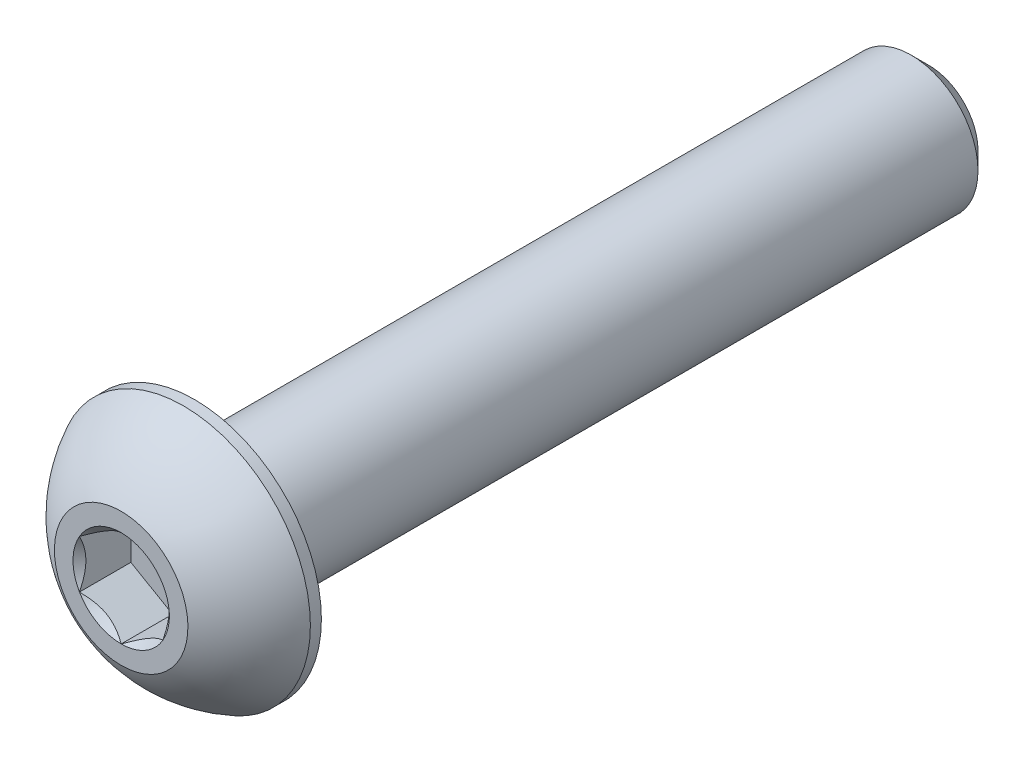
SolidWorks part; units mm, degrees
material "Alloy Steel"
ref_plane "Front" through (0, 0, 0) normal (0, 0, 1) x (1, 0, 0)
ref_plane "Top" through (0, 0, 0) normal (0, 1, 0) x (1, 0, 0)
ref_plane "Right" through (0, 0, 0) normal (1, 0, 0) x (0, 0, -1)
sketch "Sketch1" plane through (0, 0, 0) normal (1, 0, 0) x (0, 0, -1)
  line L2 (2.2, 2) -> (24.2, 2)
  line L3 (24.2, 2) -> (24.2, 0)
  line L4 (24.2, 0) -> (2.2, 0)
  line L6 (1.87, 3.8) -> (2.2, 3.8) construction
  line L7 (24.2, 2) -> (24.2, -2) construction
  line L8 (0, 0) -> (2.2, 0) construction
  line L9 (2.2, 3.8) -> (2.2, -3.8) construction
  line L11 (2.2, 2) -> (2.2, 0)
  line L13 (0, 1.25) -> (0, -1.25) construction
  line L14 (0, 1.25) -> (0, 2) construction
  line L15 (24.1562, 2.0758) -> (24.5062, 1.4696) construction
  line L16 (24.5062, 1.4696) -> (24.8562, 2.0758) construction
  line L17 (24.8562, 2.0758) -> (24.1562, 2.0758) construction
  line L18 (24.2, 2) -> (24.8125, 2) construction
  line L19 (24.5062, 2.0758) -> (24.5062, 2) construction
  line L20 (24.5062, 2) -> (24.5062, 1.5453) construction
  line L21 (24.5062, 1.5453) -> (24.5062, 1.4696) construction
  line L22 (24.4625, 1.5453) -> (24.55, 1.5453)
  line L23 (24.1781, 2.0379) -> (24.8344, 2.0379)
  line L24 (24.55, 1.5453) -> (24.8344, 2.0379)
  line L25 (24.4625, 1.5453) -> (24.1781, 2.0379)
  line L26 (23.675, 2) -> (24.2, 1.475)
  arc A3 (0, 2) -> (1.87, 3.8) centre (3.7264, 0) cw construction
  point P29 (24.5062, 2.0379)
  point P30 (22.45, -2)
  dimension "D1" = 0.33
  dimension "Pitch" = 0.7
  dimension "D3" = 0.0875
  dimension "D2" = 0.525
  dimension "D4" = 45
  dimension "D5" = 1.75
sketch "Sketch10" plane through (0, 0, 0) normal (1, 0, 0) x (0, 0, -1)
  line L0 (23.675, 2) -> (24.2, 1.475) construction
  line L1 (23.675, 2) -> (24.2, 1.475)
  line L4 (24.2, 2) -> (2.2, 2)
  line L5 (24.2, 0) -> (24.2, 2)
  line L6 (2.2, 0) -> (24.2, 0)
  line L7 (2.2, 2) -> (2.2, 0)
  line L8 (23.675, 2) -> (2.2, 2)
  line L9 (24.2, 0) -> (24.2, 1.475)
  line L10 (2.2, 0) -> (24.2, 0)
  line L11 (2.2, 2) -> (2.2, 0)
  dimension "D1" = 0
revolve "Revolve3" add sketch "Sketch10" angle 360 about L8
sketch "Sketch7" plane through (0, 0, 0) normal (1, 0, 0) x (0, 0, -1)
  line L6 (1.87, 3.8) -> (2.2, 3.8) construction
  line L8 (0, 0) -> (2.2, 0) construction
  line L11 (2.2, 3.8) -> (2.2, -3.8) construction
  line L12 (1.87, 3.8) -> (2.2, 3.8)
  line L13 (0, 0) -> (2.2, 0)
  line L14 (0, 1.25) -> (0, -1.25) construction
  line L15 (2.2, 3.8) -> (2.2, 0)
  line L16 (0, 2) -> (0, 0)
  arc A2 (1.87, 3.8) -> (0, 2) centre (3.7264, 0) ccw construction
  arc A3 (1.87, 3.8) -> (0, 2) centre (3.7264, 0) ccw
revolve "Revolve2" add sketch "Sketch7" angle 360 mid plane about L13
sketch "Sketch5" plane through (0, 0, 0) normal (0, 0, 1) x (1, 0, 0)
  line L1 (1.25, -0.7217) -> (1.25, 0.7217)
  line L2 (1.25, 0.7217) -> (0, 1.4434)
  line L3 (0, 1.4434) -> (-1.25, 0.7217)
  line L4 (-1.25, 0.7217) -> (-1.25, -0.7217)
  line L5 (-1.25, -0.7217) -> (0, -1.4434)
  line L6 (0, -1.4434) -> (1.25, -0.7217)
  circle A0 centre (0, 0) radius 1.25 construction
extrude "Cut-Extrude2" cut sketch "Sketch5" against normal blind 1.54
sketch "Sketch6" plane through (0, 0, 0) normal (0, 0, 1) x (1, 0, 0)
  circle A0 centre (0, 0) radius 1.4434
extrude "Cut-Extrude3" cut sketch "Sketch6" against normal blind 1.54 draft 45
sketch "Sketch9" [suppressed] plane through (0, 0, -2.2) normal (0, 0, -1) x (-1, 0, 0)
  circle A0 centre (0, 0) radius 2 construction
  circle A4 centre (0, 0) radius 2
split "Split1" [suppressed] bodies to split 113
sketch "Sketch11" [suppressed] plane through (0, 0, -24.2) normal (0, 0, -1) x (-1, 0, 0)
  circle A0 centre (0, 0) radius 2 construction
  circle A1 centre (0, 0) radius 2
curve "Helix/Spiral1" [suppressed] pitch 0.7 height 24.2 turns 34.5714
sketch "Sketch12" [suppressed] plane through (0, 0, 0) normal (1, 0, 0) x (0, 0, -1)
  line L0 (24.4625, 1.5453) -> (24.55, 1.5453) construction
  line L1 (24.55, 1.5453) -> (24.8344, 2.0379) construction
  line L2 (24.1781, 2.0379) -> (24.8344, 2.0379) construction
  line L3 (24.4625, 1.5453) -> (24.1781, 2.0379) construction
  line L4 (24.4625, 1.5453) -> (24.55, 1.5453)
  line L5 (24.55, 1.5453) -> (24.8344, 2.0379)
  line L6 (24.1781, 2.0379) -> (24.8344, 2.0379)
  line L7 (24.4625, 1.5453) -> (24.1781, 2.0379)
sweep "Cut-Sweep2" [suppressed] cut profiles "Sketch12" path "Helix/Spiral1"
extrude "Boss-Extrude1" [suppressed] add sketch "Sketch9" along normal blind 10 draft 45
equation "\"D1@Cut-Extrude2\" = \"Head Ht@Sketch1\" * .7"
equation "\"D1@Sketch1\" = \"Head Ht@Sketch1\" * .15"
equation "\"D1@Cut-Extrude3\" = \"D1@Cut-Extrude2\""
equation "\"D3@Sketch1\" = \"Pitch@Sketch1\" / 8"
equation "\"D2@Sketch1\"=\"Pitch@Sketch1\"*0.75"
equation "\"D3@Helix/Spiral1\" = \"Lg@Sketch1\" + \"Head Ht@Sketch1\""
equation "\"D4@Helix/Spiral1\"=\"pitch@sketch1\""
equation "\"D5@Sketch1\"=\"Pitch@Sketch1\"*2.5"
